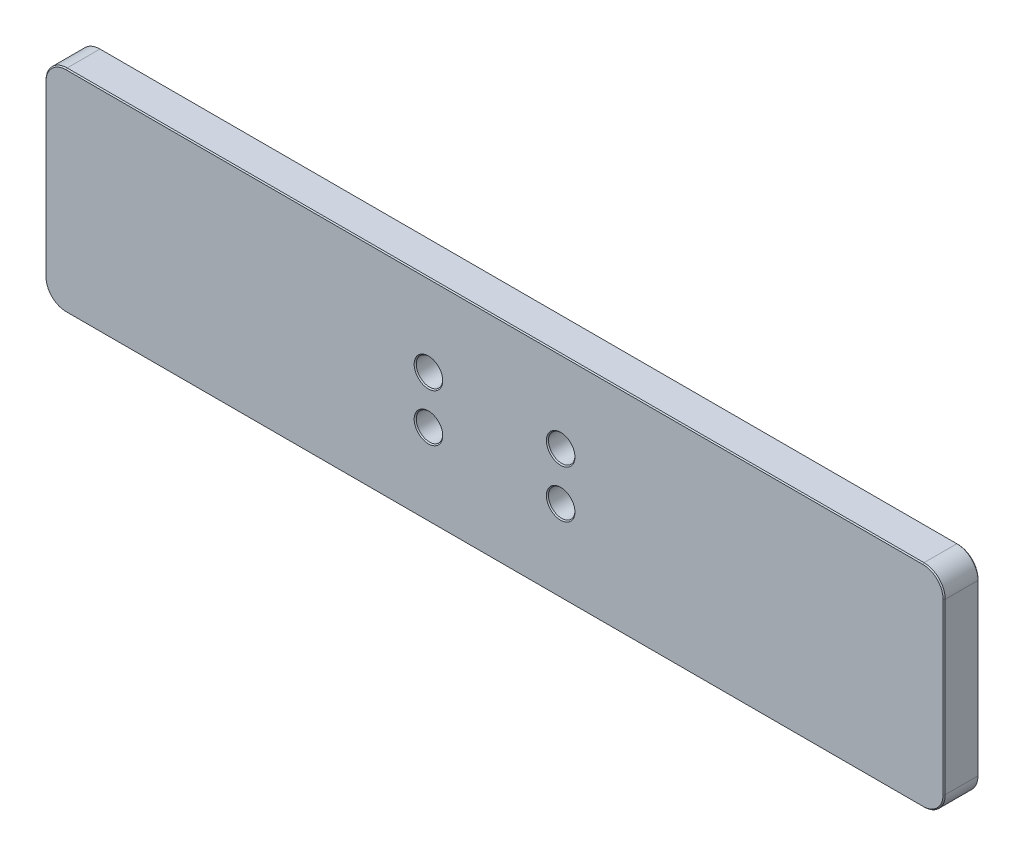
SolidWorks part; units mm, degrees
material "1060 Alloy"
ref_plane "Front Plane" through (0, 0, 0) normal (0, 0, 1) x (1, 0, 0)
ref_plane "Top Plane" through (0, 0, 0) normal (0, 1, 0) x (1, 0, 0)
ref_plane "Right Plane" through (0, 0, 0) normal (1, 0, 0) x (0, 0, -1)
sketch "Sketch1" plane through (0, 0, 0) normal (0, 0, 1) x (1, 0, 0)
  line L0 (-15.875, 5.715) -> (-15.875, -5.715) construction
  line L1 (107.95, -25.4) -> (-107.95, -25.4)
  line L2 (107.95, -25.4) -> (107.95, 25.4)
  line L3 (107.95, 25.4) -> (-107.95, 25.4)
  line L4 (-107.95, -25.4) -> (-107.95, 25.4)
  line L5 (107.95, -25.4) -> (-107.95, 25.4) construction
  line L6 (107.95, 25.4) -> (-107.95, -25.4) construction
  line L7 (-15.875, -5.715) -> (15.875, -5.715) construction
  line L8 (15.875, -5.715) -> (15.875, 5.715) construction
  line L9 (15.875, 5.715) -> (-15.875, 5.715) construction
  line L10 (15.875, -5.715) -> (-15.875, 5.715) construction
  line L11 (-15.875, -5.715) -> (15.875, 5.715) construction
  line L12 (-15.875, 5.715) -> (15.875, -5.715) construction
  line L13 (15.875, 5.715) -> (-15.875, -5.715) construction
  circle A0 centre (-15.875, 5.715) radius 3.175
  circle A1 centre (15.875, 5.715) radius 3.175
  circle A2 centre (15.875, -5.715) radius 3.175
  circle A3 centre (-15.875, -5.715) radius 3.175
  point P0 (0, 0)
  point P7 (0, 0)
  dimension "D4" = 6.35
  dimension "D1" = 215.9
  dimension "D2" = 50.8
  dimension "D3" = 31.75
  dimension "D5" = 11.43
extrude "Boss-Extrude1" add sketch "Sketch1" along normal blind 8.382
fillet "Fillet1" radius 5.08 4 edges at (-107.95, -25.4, 4.191) (107.95, -25.4, 4.191) (107.95, 25.4, 4.191) (-107.95, 25.4, 4.191)
chamfer "Chamfer1" distance 0.254 angle 45 24 edges at (-12.7, -5.715, 0) (19.05, -5.715, 0) (19.05, 5.715, 0) (-12.7, 5.715, 0) (106.4621, -23.9121, 0) (107.95, 0, 0) (106.4621, 23.9121, 0) (0, 25.4, 0) (-106.4621, 23.9121, 0) (-107.95, 0, 0) (-106.4621, -23.9121, 0) (0, -25.4, 0) (-12.7, -5.715, 8.382) (19.05, 5.715, 8.382) (-106.4621, 23.9121, 8.382) (0, 25.4, 8.382) (106.4621, 23.9121, 8.382) (107.95, 0, 8.382) (106.4621, -23.9121, 8.382) (0, -25.4, 8.382) (-106.4621, -23.9121, 8.382) (-107.95, 0, 8.382) (-12.7, 5.715, 8.382) (19.05, -5.715, 8.382)
